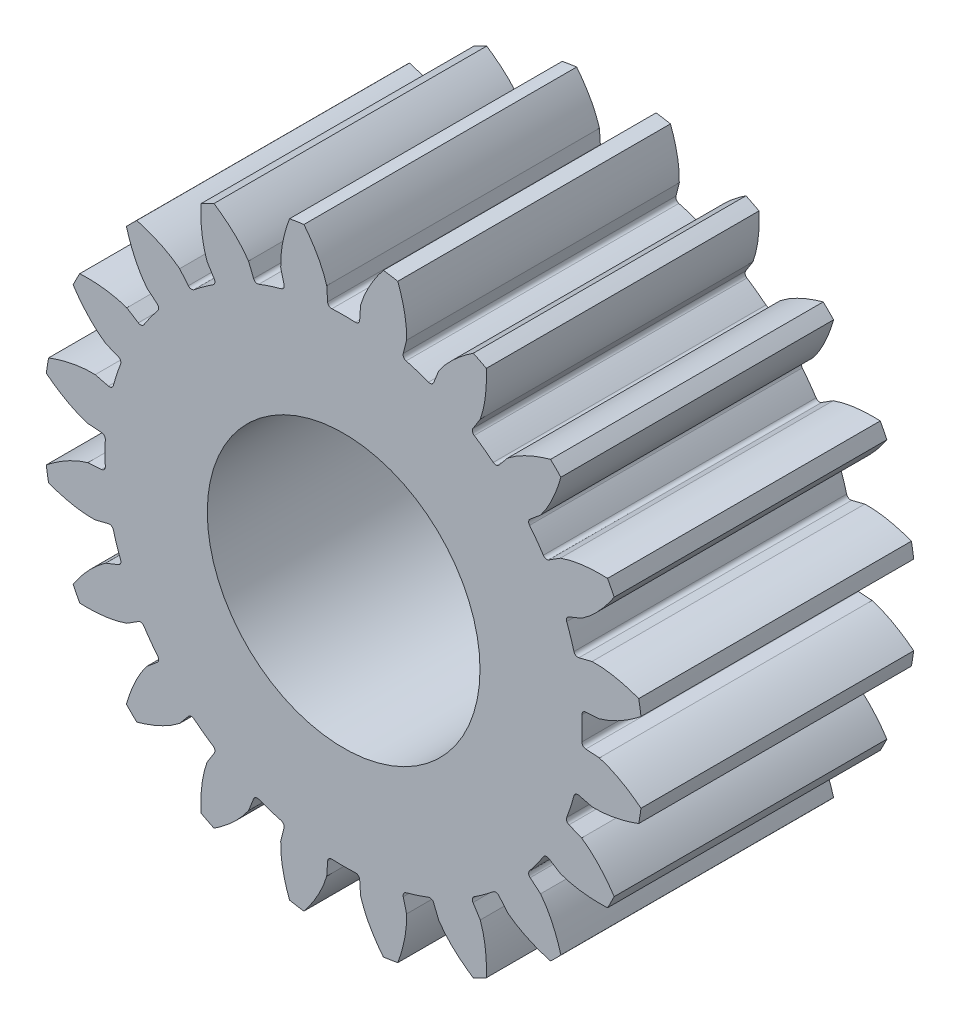
SolidWorks part; units mm, degrees
ref_plane "前视基准面" through (0, 0, 0) normal (0, 0, 1) x (1, 0, 0)
ref_plane "上视基准面" through (0, 0, 0) normal (0, 1, 0) x (1, 0, 0)
ref_plane "右视基准面" through (0, 0, 0) normal (1, 0, 0) x (0, 0, -1)
sketch "直齿轮" plane through (0, 0, 0) normal (0, 0, 1) x (1, 0, 0)
  line L0 (0, 22) -> (0, -22) construction
  line L1 (0, 0) -> (-1.2412, 18.7528)
  line L2 (0, 0) -> (1.2412, 18.7528)
  circle A0 centre (0, 0) radius 22
  arc A1 (1.5692, 19.9383) -> (-1.5692, 19.9383) centre (0, 0) ccw
  circle A2 centre (0, 0) radius 17.5
  circle A3 centre (0, 0) radius 18.7939
  spline S0 degree 4 poles (0.2659, 18.4102) (0.2649, 18.446) (0.2609, 18.5173) (0.244, 18.6594) (0.1953, 18.927) (0.1029, 19.2808) (-0.0636, 19.7645) (-0.313, 20.334) (-0.7692, 21.1924) (-1.5331, 22.3121) (-2.7874, 23.7325) (-4.6534, 25.2961) (-6.9286, 26.7014) (-9.5654, 27.8626) (-12.324, 28.6886) (-15.1573, 29.1977) (-18.1695, 29.4181) (-21.9078, 29.3008) (-26.3179, 28.5902) (-31.2686, 27.0249) (-36.4329, 24.4573) (-40.5798, 21.5858) (-43.8294, 18.7442) (-46.3202, 16.154) (-48.178, 13.9598) (-49.8972, 11.6561) (-51.4748, 9.2524) (-53.267, 6.1391) (-55.1266, 2.2434) (-56.8671, -2.4804) (-58.0048, -7.0227) (-58.6065, -10.5583) (-58.9018, -13.0664) (-59.0343, -14.4694) (-59.1236, -15.8351) (-59.1766, -16.9067) (-59.2049, -18.0395) (-59.2133, -18.6358) (-59.2152, -19.3613) (-59.2106, -19.9406) (-59.2003, -20.5131) (-59.1844, -21.0977) (-59.1575, -21.8188) (-59.1142, -22.6891) (-59.0473, -23.7001) (-58.9488, -24.8561) (-58.8284, -26.0086) (-58.7217, -26.872) (-58.6434, -27.4461) (-58.6025, -27.7331) knots 0 0 0 0 0 0.001401 0.002802 0.005604 0.010661 0.015718 0.022839 0.02996 0.048734 0.068727 0.096889 0.125051 0.153212 0.181374 0.209535 0.237696 0.271429 0.327752 0.384075 0.440398 0.496721 0.524883 0.553044 0.581206 0.609367 0.637529 0.66569 0.722013 0.778336 0.834659 0.84874 0.86282 0.876901 0.890982 0.900036 0.909091 0.914773 0.920455 0.926136 0.931818 0.9375 0.943182 0.954545 0.965909 0.977273 0.988636 1 1 1 1 1 construction
  spline S1 degree 4 poles (-1.2412, 18.7528) (-1.2647, 18.8363) (-1.3271, 19.0403) (-1.4597, 19.4089) (-1.6918, 19.9296) (-2.1447, 20.7688) (-2.9012, 21.8624) (-4.1406, 23.2478) (-5.9809, 24.7698) (-8.2217, 26.134) (-10.8157, 27.2564) (-13.5271, 28.0492) (-16.3097, 28.5307) (-19.2659, 28.7279) (-22.9323, 28.5892) (-27.254, 27.8642) (-32.1006, 26.2974) (-37.1504, 23.746) (-41.2002, 20.9029) (-44.37, 18.0949) (-46.797, 15.5381) (-48.6056, 13.374) (-50.2775, 11.1033) (-51.8099, 8.7353) (-53.5483, 5.6699) (-55.3479, 1.8367) (-57.0254, -2.8083) (-58.1127, -7.2713) (-58.6806, -10.7434) (-58.9544, -13.2057) (-59.0755, -14.5828) (-59.1544, -15.9232) (-59.1996, -16.9747) (-59.2203, -18.0861) (-59.2247, -18.6711) (-59.222, -19.3828) (-59.215, -19.8727) (-59.2072, -20.2172) (-59.2016, -20.4222) (-59.1998, -20.4858) knots 0.007195 0.007195 0.007195 0.007195 0.007195 0.010661 0.015718 0.022839 0.02996 0.048734 0.068727 0.096889 0.125051 0.153212 0.181374 0.209535 0.237696 0.271429 0.327752 0.384075 0.440398 0.496721 0.524883 0.553044 0.581206 0.609367 0.637529 0.66569 0.722013 0.778336 0.834659 0.84874 0.86282 0.876901 0.890982 0.900036 0.909091 0.914773 0.920455 0.926136 0.928685 0.928685 0.928685 0.928685 0.928685
  spline S2 degree 4 poles (-0.2659, 18.4102) (-0.2649, 18.446) (-0.2609, 18.5173) (-0.244, 18.6594) (-0.1953, 18.927) (-0.1029, 19.2808) (0.0636, 19.7645) (0.313, 20.334) (0.7692, 21.1924) (1.5331, 22.3121) (2.7874, 23.7325) (4.6534, 25.2961) (6.9286, 26.7014) (9.5654, 27.8626) (12.324, 28.6886) (15.1573, 29.1977) (18.1695, 29.4181) (21.9078, 29.3008) (26.3179, 28.5902) (31.2686, 27.0249) (36.4329, 24.4573) (40.5798, 21.5858) (43.8294, 18.7442) (46.3202, 16.154) (48.178, 13.9598) (49.8972, 11.6561) (51.4748, 9.2524) (53.267, 6.1391) (55.1266, 2.2434) (56.8671, -2.4804) (58.0048, -7.0227) (58.6065, -10.5583) (58.9018, -13.0664) (59.0343, -14.4694) (59.1236, -15.8351) (59.1766, -16.9067) (59.2049, -18.0395) (59.2133, -18.6358) (59.2152, -19.3613) (59.2106, -19.9406) (59.2003, -20.5131) (59.1844, -21.0977) (59.1575, -21.8188) (59.1142, -22.6891) (59.0473, -23.7001) (58.9488, -24.8561) (58.8284, -26.0086) (58.7217, -26.872) (58.6434, -27.4461) (58.6025, -27.7331) knots 0 0 0 0 0 0.001401 0.002802 0.005604 0.010661 0.015718 0.022839 0.02996 0.048734 0.068727 0.096889 0.125051 0.153212 0.181374 0.209535 0.237696 0.271429 0.327752 0.384075 0.440398 0.496721 0.524883 0.553044 0.581206 0.609367 0.637529 0.66569 0.722013 0.778336 0.834659 0.84874 0.86282 0.876901 0.890982 0.900036 0.909091 0.914773 0.920455 0.926136 0.931818 0.9375 0.943182 0.954545 0.965909 0.977273 0.988636 1 1 1 1 1 construction
  spline S3 degree 4 poles (1.2412, 18.7528) (1.2647, 18.8363) (1.3271, 19.0403) (1.4597, 19.4089) (1.6918, 19.9296) (2.1447, 20.7688) (2.9012, 21.8624) (4.1406, 23.2478) (5.9809, 24.7698) (8.2217, 26.134) (10.8157, 27.2564) (13.5271, 28.0492) (16.3097, 28.5307) (19.2659, 28.7279) (22.9323, 28.5892) (27.254, 27.8642) (32.1006, 26.2974) (37.1504, 23.746) (41.2002, 20.9029) (44.37, 18.0949) (46.797, 15.5381) (48.6056, 13.374) (50.2775, 11.1033) (51.8099, 8.7353) (53.5483, 5.6699) (55.3479, 1.8367) (57.0254, -2.8083) (58.1127, -7.2713) (58.6806, -10.7434) (58.9544, -13.2057) (59.0755, -14.5828) (59.1544, -15.9232) (59.1996, -16.9747) (59.2203, -18.0861) (59.2247, -18.6711) (59.222, -19.3828) (59.215, -19.8727) (59.2072, -20.2172) (59.2016, -20.4222) (59.1998, -20.4858) knots 0.007195 0.007195 0.007195 0.007195 0.007195 0.010661 0.015718 0.022839 0.02996 0.048734 0.068727 0.096889 0.125051 0.153212 0.181374 0.209535 0.237696 0.271429 0.327752 0.384075 0.440398 0.496721 0.524883 0.553044 0.581206 0.609367 0.637529 0.66569 0.722013 0.778336 0.834659 0.84874 0.86282 0.876901 0.890982 0.900036 0.909091 0.914773 0.920455 0.926136 0.928685 0.928685 0.928685 0.928685 0.928685
  dimension "齿顶圆" = 44
  dimension "分度圆" = 40
  dimension "齿根圆" = 35
  dimension "基圆直径" = 37.5877
  dimension "D1" = 3.1416
extrude "齿轮毛坯" add sketch "直齿轮" along normal mid plane 20 contours A0
chamfer "轮齿倒角" [suppressed] distance 0 angle 45
sketch "草图2" plane through (0, 0, 0) normal (0, 0, 1) x (1, 0, 0)
  line L0 (0, 0) -> (-1.2412, 18.7528) construction
  line L1 (0, 0) -> (1.2412, 18.7528) construction
  line L2 (0, 0) -> (-1.2412, 18.7528)
  line L3 (0, 0) -> (1.2412, 18.7528)
  circle A0 centre (0, 0) radius 22 construction
  circle A1 centre (0, 0) radius 22
  circle A2 centre (0, 0) radius 17.5 construction
  circle A3 centre (0, 0) radius 17.5
  spline S0 degree 4 poles (-1000.8844, -2.5565) (-27.8409, 1.7671) (-1.7741, 9.2788) (0.3535, 15.3398) (-1.6918, 19.9296) (-2.1447, 20.7688) (-2.9012, 21.8624) (-4.1406, 23.2478) (-5.9809, 24.7698) (-8.2217, 26.134) (-10.8157, 27.2564) (-13.5271, 28.0492) (-16.3097, 28.5307) (-19.2659, 28.7279) (-22.9323, 28.5892) (-27.254, 27.8642) (-32.1006, 26.2974) (-37.1504, 23.746) (-41.2002, 20.9029) (-44.37, 18.0949) (-46.797, 15.5381) (-48.6056, 13.374) (-50.2775, 11.1033) (-51.8099, 8.7353) (-53.5483, 5.6699) (-55.3479, 1.8367) (-57.0254, -2.8083) (-58.1127, -7.2713) (-58.6806, -10.7434) (-58.9544, -13.2057) (-59.0755, -14.5828) (-59.1544, -15.9232) (-59.1996, -16.9747) (-59.2203, -18.0861) (-59.2247, -18.6711) (-59.222, -19.3828) (-59.1569, -23.9026) (-58.6529, -27.7473) (-57.8793, -51.4705) (-51.3281, 979.3767) knots -0.17068 -0.17068 -0.17068 -0.17068 -0.17068 0.010661 0.015718 0.022839 0.02996 0.048734 0.068727 0.096889 0.125051 0.153212 0.181374 0.209535 0.237696 0.271429 0.327752 0.384075 0.440398 0.496721 0.524883 0.553044 0.581206 0.609367 0.637529 0.66569 0.722013 0.778336 0.834659 0.84874 0.86282 0.876901 0.890982 0.900036 0.909091 0.914773 0.920455 0.926136 1.089856 1.089856 1.089856 1.089856 1.089856 only from (-1.2412, 18.7528) to (-59.1998, -20.4858) construction
  spline S1 degree 4 poles (-1.2412, 18.7528) (-1.2647, 18.8363) (-1.3271, 19.0403) (-1.4597, 19.4089) (-1.6918, 19.9296) (-2.1447, 20.7688) (-2.9012, 21.8624) (-4.1406, 23.2478) (-5.9809, 24.7698) (-8.2217, 26.134) (-10.8157, 27.2564) (-13.5271, 28.0492) (-16.3097, 28.5307) (-19.2659, 28.7279) (-22.9323, 28.5892) (-27.254, 27.8642) (-32.1006, 26.2974) (-37.1504, 23.746) (-41.2002, 20.9029) (-44.37, 18.0949) (-46.797, 15.5381) (-48.6056, 13.374) (-50.2775, 11.1033) (-51.8099, 8.7353) (-53.5483, 5.6699) (-55.3479, 1.8367) (-57.0254, -2.8083) (-58.1127, -7.2713) (-58.6806, -10.7434) (-58.9544, -13.2057) (-59.0755, -14.5828) (-59.1544, -15.9232) (-59.1996, -16.9747) (-59.2203, -18.0861) (-59.2247, -18.6711) (-59.222, -19.3828) (-59.215, -19.8727) (-59.2072, -20.2172) (-59.2016, -20.4222) (-59.1998, -20.4858) knots 0.007195 0.007195 0.007195 0.007195 0.007195 0.010661 0.015718 0.022839 0.02996 0.048734 0.068727 0.096889 0.125051 0.153212 0.181374 0.209535 0.237696 0.271429 0.327752 0.384075 0.440398 0.496721 0.524883 0.553044 0.581206 0.609367 0.637529 0.66569 0.722013 0.778336 0.834659 0.84874 0.86282 0.876901 0.890982 0.900036 0.909091 0.914773 0.920455 0.926136 0.928685 0.928685 0.928685 0.928685 0.928685
  spline S2 degree 4 poles (1000.8844, -2.5565) (27.8409, 1.7671) (1.7741, 9.2788) (-0.3535, 15.3398) (1.6918, 19.9296) (2.1447, 20.7688) (2.9012, 21.8624) (4.1406, 23.2478) (5.9809, 24.7698) (8.2217, 26.134) (10.8157, 27.2564) (13.5271, 28.0492) (16.3097, 28.5307) (19.2659, 28.7279) (22.9323, 28.5892) (27.254, 27.8642) (32.1006, 26.2974) (37.1504, 23.746) (41.2002, 20.9029) (44.37, 18.0949) (46.797, 15.5381) (48.6056, 13.374) (50.2775, 11.1033) (51.8099, 8.7353) (53.5483, 5.6699) (55.3479, 1.8367) (57.0254, -2.8083) (58.1127, -7.2713) (58.6806, -10.7434) (58.9544, -13.2057) (59.0755, -14.5828) (59.1544, -15.9232) (59.1996, -16.9747) (59.2203, -18.0861) (59.2247, -18.6711) (59.222, -19.3828) (59.1569, -23.9026) (58.6529, -27.7473) (57.8793, -51.4705) (51.3281, 979.3767) knots -0.17068 -0.17068 -0.17068 -0.17068 -0.17068 0.010661 0.015718 0.022839 0.02996 0.048734 0.068727 0.096889 0.125051 0.153212 0.181374 0.209535 0.237696 0.271429 0.327752 0.384075 0.440398 0.496721 0.524883 0.553044 0.581206 0.609367 0.637529 0.66569 0.722013 0.778336 0.834659 0.84874 0.86282 0.876901 0.890982 0.900036 0.909091 0.914773 0.920455 0.926136 1.089856 1.089856 1.089856 1.089856 1.089856 only from (1.2412, 18.7528) to (59.1998, -20.4858) construction
  spline S3 degree 4 poles (1.2412, 18.7528) (1.2647, 18.8363) (1.3271, 19.0403) (1.4597, 19.4089) (1.6918, 19.9296) (2.1447, 20.7688) (2.9012, 21.8624) (4.1406, 23.2478) (5.9809, 24.7698) (8.2217, 26.134) (10.8157, 27.2564) (13.5271, 28.0492) (16.3097, 28.5307) (19.2659, 28.7279) (22.9323, 28.5892) (27.254, 27.8642) (32.1006, 26.2974) (37.1504, 23.746) (41.2002, 20.9029) (44.37, 18.0949) (46.797, 15.5381) (48.6056, 13.374) (50.2775, 11.1033) (51.8099, 8.7353) (53.5483, 5.6699) (55.3479, 1.8367) (57.0254, -2.8083) (58.1127, -7.2713) (58.6806, -10.7434) (58.9544, -13.2057) (59.0755, -14.5828) (59.1544, -15.9232) (59.1996, -16.9747) (59.2203, -18.0861) (59.2247, -18.6711) (59.222, -19.3828) (59.215, -19.8727) (59.2072, -20.2172) (59.2016, -20.4222) (59.1998, -20.4858) knots 0.007195 0.007195 0.007195 0.007195 0.007195 0.010661 0.015718 0.022839 0.02996 0.048734 0.068727 0.096889 0.125051 0.153212 0.181374 0.209535 0.237696 0.271429 0.327752 0.384075 0.440398 0.496721 0.524883 0.553044 0.581206 0.609367 0.637529 0.66569 0.722013 0.778336 0.834659 0.84874 0.86282 0.876901 0.890982 0.900036 0.909091 0.914773 0.920455 0.926136 0.928685 0.928685 0.928685 0.928685 0.928685
extrude "插齿" cut sketch "草图2" against normal mid plane 20 contours A3 S3 A1 S1 region at (0, 20.106, 0)
fillet "圆角1" radius 0.3 2 edges at (1.1557, 17.4618, 0) (-1.1557, 17.4618, 0)
pattern_circular "圆周阵列1" count 20 over 360 about axis through (0, 0, 10) along (0, 0, -1) of "插齿", "圆角1"
fillet "圆角2" [suppressed] radius 0.3
pattern_circular "圆周阵列2" [suppressed] count 20 over 360 of bodies 102
pattern_circular "圆周阵列3" [suppressed] count 20 over 360 of bodies 102
sketch "分度圆" plane through (0, 0, 0) normal (0, 0, 1) x (1, 0, 0)
  circle A0 centre (0, 0) radius 20 construction
sketch "草图3" plane through (0, 0, 10) normal (0, 0, 1) x (1, 0, 0)
  circle A0 centre (0, 0) radius 10
  dimension "D1" = 20
extrude "切除-拉伸1" cut sketch "草图3" against normal through all
equation "\"m\"= 2'模数"
equation "\"z\" = 20'齿数"
equation "\"a\"= 20'压力角（常见为20°）"
equation "\"B\"= 20'齿宽"
equation "\"C1\"= 0'轮齿倒角（若设为0，则无倒角）"
equation "\"R\"= 0.3'齿根圆角（若设为0，则无圆角）"
equation "\"x\"= 0'变位系数"
equation "\"ha\"= 1'齿顶高系数"
equation "\"c\"= 0.25'顶隙系数"
equation "\"分度圆@直齿轮\"=\"m\" * \"z\""
equation "\"齿顶圆@直齿轮\" = \"m\" * ( \"z\" + 2 * ( \"ha\" + \"x\" ) )"
equation "\"齿根圆@直齿轮\" = \"m\" * ( \"z\" - 2 * ( \"ha\" - \"x\" + \"c\" ) )"
equation "\"基圆直径@直齿轮\"= \"m\" * \"z\" * cos ( \"a\" )"
equation "\"D1@直齿轮\"= \"m\" * ( pi / 2 ) - 2 * \"m\" * tan ( \"a\" ) * \"x\"'作者：机械菌-"
equation "\"圆周阵列3\"= IIF ( \"R\">0 , \"suppressed\" , \"unsuppressed\" )"
equation "\"圆角1\"=IIF ( \"R\">0 ,IIF ( \"m\" * ( \"z\" - 2 * ( \"ha\" - \"x\" + \"c\" ) ) < \"m\" * \"z\" * cos ( \"a\" ) , \"unsuppressed\" , \"suppressed\" ) , \"suppressed\" )"
equation "\"圆周阵列1\"=IIF ( \"R\">0 , IIF ( \"m\" * ( \"z\" - 2 * ( \"ha\" - \"x\" + \"c\" ) ) < \"m\" * \"z\" * cos ( \"a\" ) , \"unsuppressed\" , \"suppressed\" ), \"suppressed\" )"
equation "\"圆角2\"=IIF ( \"R\">0 ,IIF ( \"m\" * ( \"z\" - 2 * ( \"ha\" - \"x\" + \"c\" ) ) > \"m\" * \"z\" * cos ( \"a\" ) , \"unsuppressed\" , \"suppressed\" ) , \"suppressed\" )"
equation "\"圆周阵列2\"=IIF ( \"R\">0 , IIF ( \"m\" * ( \"z\" - 2 * ( \"ha\" - \"x\" + \"c\" ) ) > \"m\" * \"z\" * cos ( \"a\" ) , \"unsuppressed\" , \"suppressed\" ), \"suppressed\" )"
equation "\"轮齿倒角\"= IIF ( \"C1\" > 0 , \"unsuppressed\" , \"suppressed\" )"
